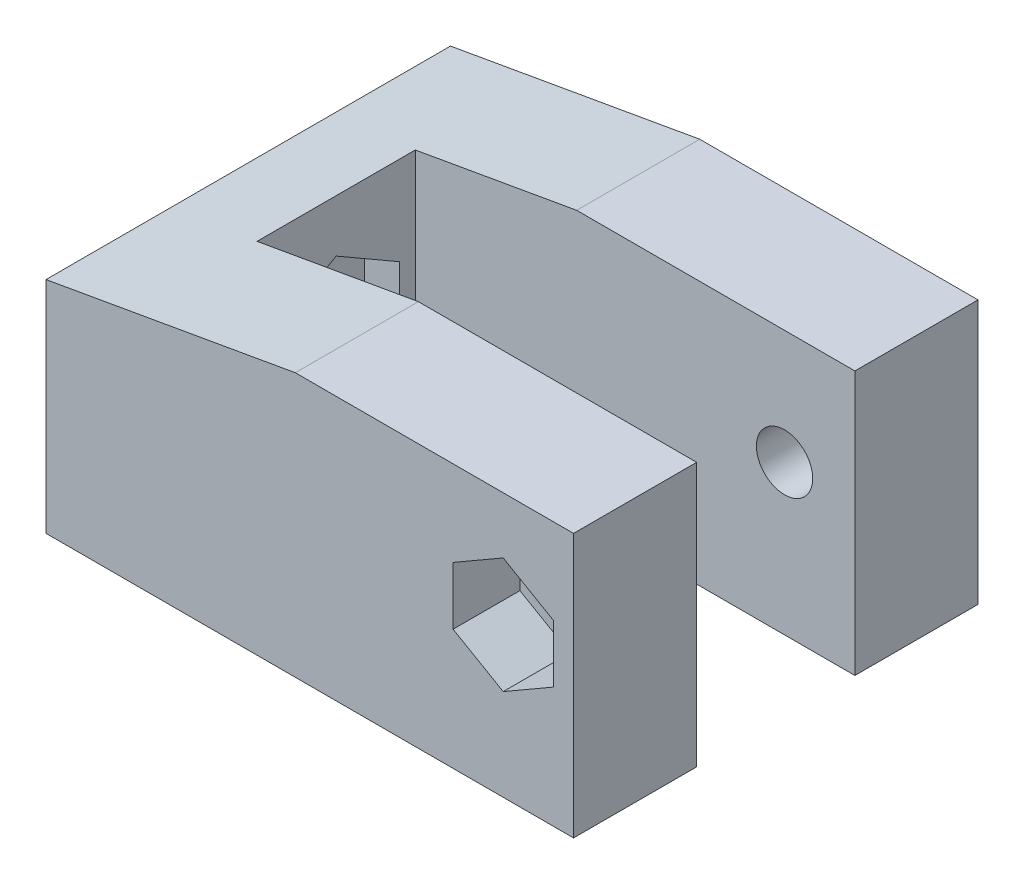
SolidWorks part; units mm, degrees
ref_plane "Front Plane" through (0, 0, 0) normal (0, 0, 1) x (1, 0, 0)
ref_plane "Top Plane" through (0, 0, 0) normal (0, 1, 0) x (1, 0, 0)
ref_plane "Right Plane" through (0, 0, 0) normal (1, 0, 0) x (0, 0, -1)
sketch "Sketch1" plane through (0, 0, 0) normal (1, 0, 0) x (0, 0, -1)
  line L1 (0, 0) -> (23, 0)
  line L2 (0, 0) -> (0, 15)
  line L3 (0, 15) -> (23, 15)
  line L4 (23, 0) -> (23, 15)
  dimension "D1" = 23
  dimension "D2" = 15
extrude "Boss-Extrude1" add sketch "Sketch1" along normal blind 30
sketch "Sketch2" plane through (30, 0, 0) normal (1, 0, 0) x (0, 0, -1)
  line L0 (11.5, 15) -> (11.5, 0) construction
  line L1 (7, 15) -> (16, 15)
  line L2 (7, 15) -> (7, 0)
  line L3 (7, 0) -> (16, 0)
  line L4 (16, 15) -> (16, 0)
  line L5 (0, 0) -> (23, 0) construction
  line L8 (23, 15) -> (0, 15) construction
  line L9 (11.5, 15) -> (11.5, 0) construction
  dimension "D1" = 9
extrude "Cut-Extrude1" cut sketch "Sketch2" against normal offset from surface (25 mm away) 5 up to face at (0, 7.5, -11.5)
sketch "Sketch3" plane through (0, 0, -23) normal (0, 0, -1) x (-1, 0, 0)
  line L1 (-30, 0) -> (-30, 15) construction
  line L2 (-30, 0) -> (0, 0) construction
  circle A0 centre (-26, 8.5) radius 1.6
  dimension "D3" = 3.2
  dimension "D1" = 8.5
  dimension "D2" = 4
extrude "Cut-Extrude2" cut sketch "Sketch3" against normal through all both and the other way through all
chamfer "Chamfer1" distance 2.5 angle 80 1 edges at (0, 15, -11.5) first distance on face at (0, 7.5, -11.5)
sketch "Sketch4" plane through (0, 0, 0) normal (-1, 0, 0) x (0, 0, 1)
  line L0 (-11.5, 12.5) -> (-11.5, 0) construction
  line L1 (0, 12.5) -> (-23, 12.5) construction
  line L2 (0, 0) -> (-23, 0) construction
  line L3 (-23, 6.25) -> (0, 6.25) construction
  line L4 (-23, 0) -> (-23, 12.5) construction
  line L5 (0, 12.5) -> (0, 0) construction
  circle A0 centre (-11.5, 6.25) radius 2.2
  dimension "D1" = 4.4
extrude "Cut-Extrude3" cut sketch "Sketch4" against normal blind 10
sketch "Sketch5" plane through (5, 0, 0) normal (1, 0, 0) x (0, 0, -1)
  line L1 (7.9, 8.3285) -> (7.9, 4.1715)
  line L2 (7.9, 4.1715) -> (11.5, 2.0931)
  line L3 (11.5, 2.0931) -> (15.1, 4.1715)
  line L4 (15.1, 4.1715) -> (15.1, 8.3285)
  line L5 (15.1, 8.3285) -> (11.5, 10.4069)
  line L6 (11.5, 10.4069) -> (7.9, 8.3285)
  circle A0 centre (11.5, 6.25) radius 3.6 construction
  dimension "D1" = 7.2
extrude "Cut-Extrude4" cut sketch "Sketch5" against normal blind 2
sketch "Sketch6" plane through (0, 0, -23) normal (0, 0, -1) x (-1, 0, 0)
  circle A0 centre (-26, 8.5) radius 3.25
  dimension "D1" = 6.5
extrude "Cut-Extrude5" cut sketch "Sketch6" against normal blind 2.5
sketch "Sketch7" plane through (0, 0, 0) normal (0, 0, 1) x (1, 0, 0)
  line L1 (23.15, 10.1454) -> (23.15, 6.8546)
  line L2 (23.15, 6.8546) -> (26, 5.2091)
  line L3 (26, 5.2091) -> (28.85, 6.8546)
  line L4 (28.85, 6.8546) -> (28.85, 10.1454)
  line L5 (28.85, 10.1454) -> (26, 11.7909)
  line L6 (26, 11.7909) -> (23.15, 10.1454)
  circle A0 centre (26, 8.5) radius 2.85 construction
  dimension "D1" = 5.7
extrude "Cut-Extrude6" cut sketch "Sketch7" against normal blind 3.8
